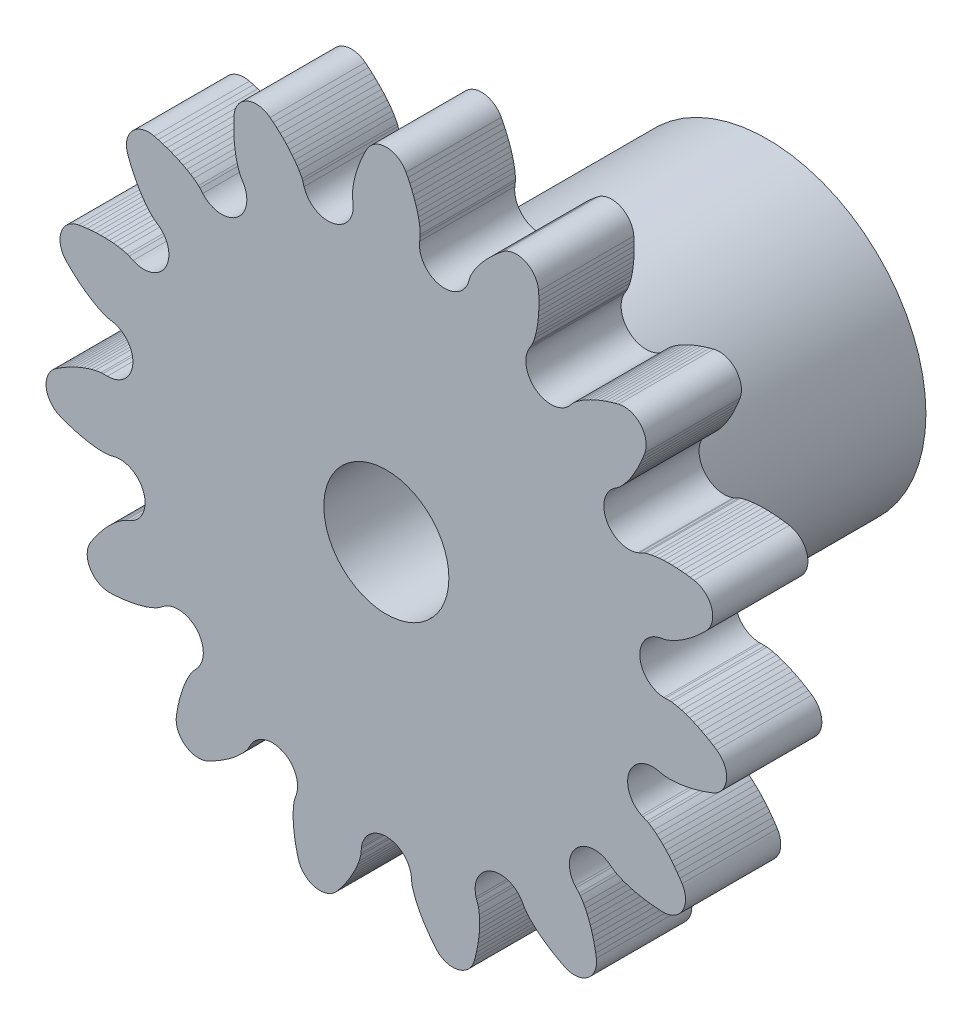
SolidWorks part; units mm, degrees
material "Delrin 2700 NC010, Low Viscosity Acetal Copolymer (SS)"
ref_plane "Front Plane" through (0, 0, 0) normal (0, 0, 1) x (1, 0, 0)
ref_plane "Top Plane" through (0, 0, 0) normal (0, 1, 0) x (1, 0, 0)
ref_plane "Right Plane" through (0, 0, 0) normal (1, 0, 0) x (0, 0, -1)
sketch "Sketch4" plane through (0, 0, 0) normal (0, 0, 1) x (1, 0, 0)
  circle A0 centre (0, 0) radius 4.0804
  circle A1 centre (0, 0) radius 12.065 construction
  dimension "D1" = 24.13
extrude "Boss-Extrude2" add sketch "Sketch4" along normal blind 3.81
sketch "Sketch1" plane through (0, 0, 0) normal (0, 0, 1) x (1, 0, 0)
  line L0 (-5.7272, 9.5849) -> (0, 0)
  line L1 (0, 0) -> (-1.3313, 11.0854)
  line L2 (-5.8155, 9.7327) -> (-5.7272, 9.5849)
  line L3 (-3.3434, 10.8333) -> (-3.2926, 10.6687)
  arc A0 (-3.2926, 10.6687) -> (-1.3313, 11.0854) centre (-2.3308, 10.9654) ccw
  circle A1 centre (0, 0) radius 12.065 construction
  arc A33 (-5.8525, 9.8057) -> (-5.8155, 9.7327) centre (-5.3132, 10.0327) ccw
  arc A34 (-3.3434, 10.8333) -> (-3.373, 10.9097) centre (-3.9025, 10.6608) ccw
  arc A35 (-5.9349, 10.0323) -> (-5.8525, 9.8057) centre (-3.5988, 10.7544) ccw
  arc A36 (-3.373, 10.9097) -> (-3.4862, 11.1226) centre (-5.5859, 9.8696) ccw
  arc A37 (-5.977, 10.1826) -> (-5.9349, 10.0323) centre (-3.1465, 10.8942) ccw
  arc A38 (-3.4862, 11.1226) -> (-3.5697, 11.2544) centre (-5.9925, 9.627) ccw
  arc A39 (-6.0158, 10.3542) -> (-5.977, 10.1826) centre (-2.4021, 11.0813) ccw
  arc A40 (-3.5697, 11.2544) -> (-3.6713, 11.3981) centre (-6.6296, 9.1991) ccw
  arc A41 (-6.045, 10.5161) -> (-6.0158, 10.3542) centre (-2.0806, 11.146) ccw
  arc A42 (-3.6713, 11.3981) -> (-3.7721, 11.5281) centre (-6.8928, 9.0034) ccw
  arc A43 (-6.0693, 10.6909) -> (-6.045, 10.5161) centre (-1.4885, 11.24) ccw
  arc A44 (-3.7721, 11.5281) -> (-3.8857, 11.6631) centre (-7.359, 8.6263) ccw
  arc A45 (-6.0867, 10.8606) -> (-6.0693, 10.6909) centre (-1.2164, 11.2726) ccw
  arc A46 (-3.8857, 11.6631) -> (-4.0002, 11.7896) centre (-7.5652, 8.446) ccw
  arc A47 (-6.0988, 11.0396) -> (-6.0867, 10.8606) centre (-0.7032, 11.3161) ccw
  arc A48 (-4.0002, 11.7896) -> (-4.1251, 11.9183) centre (-7.9409, 8.0936) ccw
  arc A49 (-6.1051, 11.2154) -> (-6.0988, 11.0396) centre (-0.4614, 11.3284) ccw
  arc A50 (-4.1251, 11.9183) -> (-4.2515, 12.0406) centre (-8.1119, 7.9222) ccw
  arc A51 (-6.106, 11.3984) -> (-6.1051, 11.2154) centre (0.0007, 11.3377) ccw
  arc A52 (-4.2515, 12.0406) -> (-4.3869, 12.1638) centre (-8.428, 7.585) ccw
  arc A53 (-6.1016, 11.5792) -> (-6.106, 11.3984) centre (0.2213, 11.3355) ccw
  arc A54 (-4.3869, 12.1638) -> (-4.5243, 12.2815) centre (-8.574, 7.4196) ccw
  arc A55 (-5.8546, 13.1469) -> (-6.1016, 11.5792) centre (0.6465, 11.3191) ccw
  arc A56 (-4.5243, 12.2815) -> (-5.8546, 13.1469) centre (-8.8463, 7.0927) ccw
  dimension "D1" = 24.13
  dimension "D2" = 1.0066
  dimension "D3" = 0.1723
  dimension "D4" = 24.011
extrude "Boss-Extrude1" add sketch "Sketch1" along normal up to surface (3.81 mm away) up to face at (4.0804, 0, 3.81)
fillet "Fillet1" radius 0.889 1 edges at (-5.8546, 13.1469, 1.905)
pattern_circular "CirPattern2" count 15 over 360 about axis through (0, 0, 3.81) along (0, 0, -1) of "Boss-Extrude1", "Fillet1"
sketch "Sketch5" plane through (0, 0, 3.81) normal (0, 0, 1) x (1, 0, 0)
  circle A0 centre (0, 0) radius 2.5019
  dimension "D1" = 5.0038
extrude "Cut-Extrude1" cut sketch "Sketch5" against normal through all
sketch "Sketch6" plane through (0, 0, 0) normal (0, 0, 1) x (1, 0, 0)
  circle A0 centre (0, 0) radius 6.35
  circle A1 centre (0, 0) radius 2.5019 construction
  circle A2 centre (0, 0) radius 2.5019
  dimension "D1" = 12.7
extrude "Boss-Extrude3" add sketch "Sketch6" against normal blind 11.43
